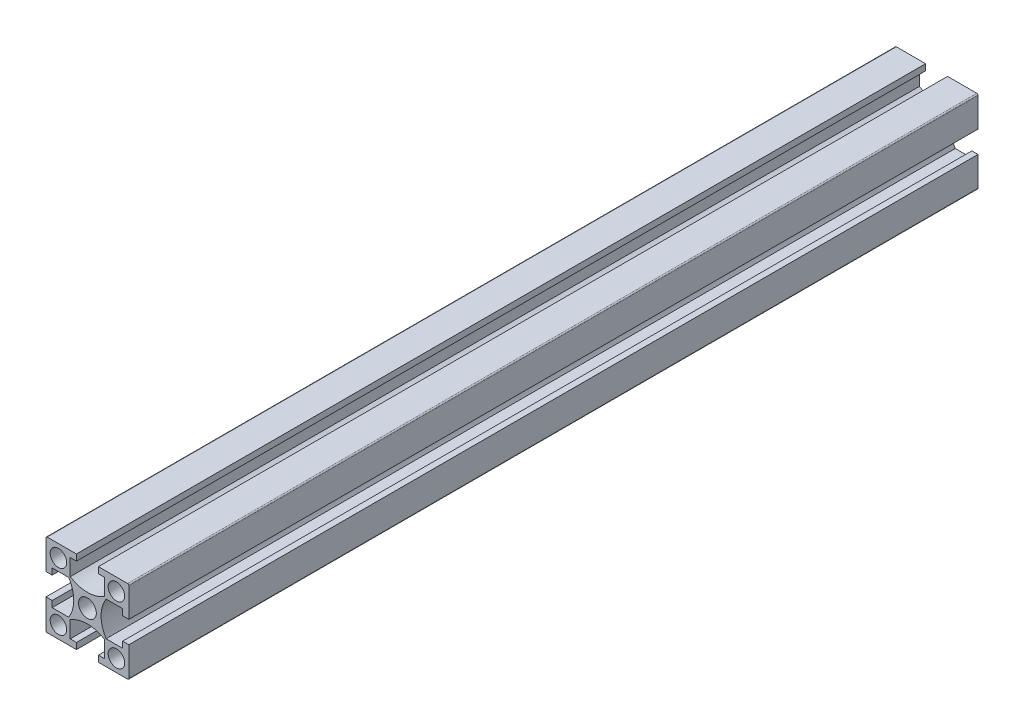
SolidWorks part; units mm, degrees
ref_plane "정면" through (0, 0, 0) normal (0, 0, 1) x (1, 0, 0)
ref_plane "윗면" through (0, 0, 0) normal (0, 1, 0) x (1, 0, 0)
ref_plane "우측면" through (0, 0, 0) normal (1, 0, 0) x (0, 0, -1)
sketch "스케치1" plane through (0, 0, 0) normal (0, 0, 1) x (1, 0, 0)
  line L0 (0, 32.0265) -> (0, -31.6588) construction
  line L1 (-10, 10) -> (-10, -10)
  line L2 (-10, 10) -> (10, 10)
  line L3 (-10, 2.65) -> (-8.5, 2.65)
  line L4 (13.6618, 0) -> (-11.6993, 0) construction
  line L5 (-8.5, 2.65) -> (-8.5, 4.15)
  line L6 (-8.5, 4.15) -> (-4.5032, 4.15)
  line L7 (-10, -2.65) -> (-8.5, -2.65)
  line L8 (-8.5, -2.65) -> (-8.5, -4.15)
  line L9 (-8.5, -4.15) -> (-4.5032, -4.15)
  line L10 (-10, -10) -> (10, -10)
  line L11 (10, 10) -> (10, -10)
  circle A0 centre (-7, 7) radius 2
  circle A1 centre (-7, -7) radius 2
  arc A2 (-4.5032, 4.15) -> (-4.5032, -4.15) centre (-11.0587, 0) cw
  circle A3 centre (0, 0) radius 2.15
  circle A4 centre (7, 7) radius 2
  circle A5 centre (7, -7) radius 2
  point P21 (-10, 0)
  point P23 (-3.3, 0)
  point P31 (0, -10)
  point P32 (0, 10)
  dimension "D3" = 4
  dimension "D9" = 6.7
  dimension "D10" = 4.3
  dimension "D11" = 7.7587
  dimension "D1" = 20
  dimension "D2" = 20
  dimension "D4" = 14
  dimension "D5" = 14
  dimension "D6" = 5.3
  dimension "D7" = 8.3
  dimension "D8" = 1.5
extrude "보스-돌출1" add sketch "스케치1" along normal blind 205 contours A0 | A4 | A3 | A5 | A1 | A2 L6 L5 L3 L1 L7 L8 L9 | L2 L11 L10 L1 region at (-6.6069, 0, 0) region at (-7, 7, 0) region at (-7, -7, 0) region at (0, 0, 0) region at (7, 7, 0) region at (7, -7, 0)
extrude "컷-돌출1" cut sketch "스케치1<3>" along normal up to next contours A2 L6 L5 L3 L1 L7 L8 L9 region at (-6.6069, 0, 0)
sketch "스케치1<3>" plane through (0, 0, 0) normal (0, 0, 1) x (1, 0, 0) same geometry as "스케치1"
pattern_circular "원형 패턴1" count 4 over 360 about axis through (0, 0, 205) along (0, 0, -1) of "컷-돌출1" reverse direction yes
fillet "필렛1" radius 0.3 4 edges at (10, -10, 102.5) (-10, -10, 102.5) (-10, 10, 102.5) (10, 10, 102.5)
sketch "스케치2" plane through (0, 10, 0) normal (0, 1, 0) x (1, 0, 0)
  line L0 (-9.7, -20) -> (9.7, -20) construction
  line L1 (-9.7, 0) -> (-9.7, -205) construction
  line L2 (9.7, -205) -> (9.7, 0) construction
  line L3 (4.15, 0) -> (-4.15, 0) construction
  circle A0 centre (0, -194) radius 2.5
  circle A1 centre (0, -31) radius 2.5
  dimension "D1" = 11
  dimension "D3" = 11
  dimension "D2" = 20
extrude "컷-돌출2" cut sketch "스케치2" against normal through all
